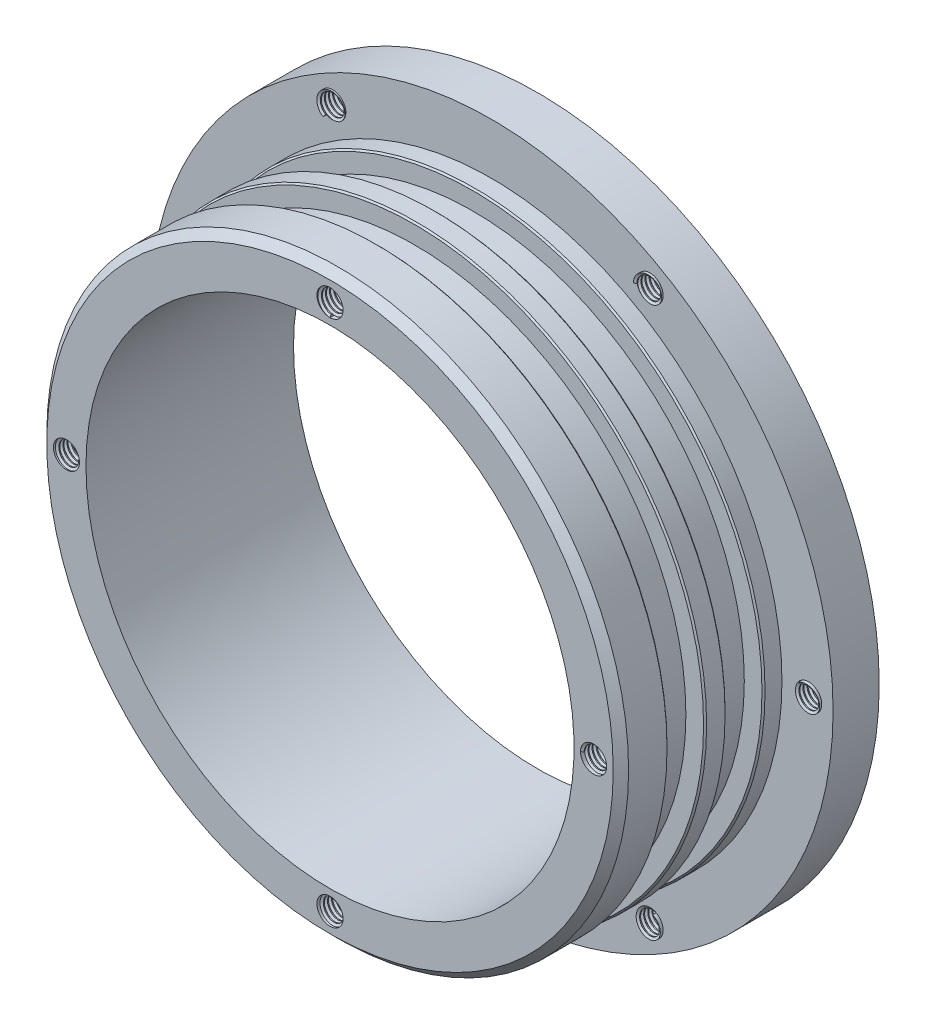
SolidWorks part; units mm, degrees
material "1060 Alloy"
ref_plane "Front Plane" through (0, 0, 0) normal (0, 0, 1) x (1, 0, 0)
ref_plane "Top Plane" through (0, 0, 0) normal (0, 1, 0) x (1, 0, 0)
ref_plane "Right Plane" through (0, 0, 0) normal (1, 0, 0) x (0, 0, -1)
sketch "Sketch1" plane through (0, 0, 0) normal (0, 1, 0) x (1, 0, 0)
  line L2 (37.8, 21) -> (44.45, 21)
  line L3 (44.45, 21) -> (44.45, 27)
  line L4 (44.45, 27) -> (0, 27)
  line L8 (37.846, 1) -> (37.846, 6)
  line L9 (37.646, 6.2) -> (35.3, 6.2)
  line L10 (35.3, 6.2) -> (35.3, 11)
  line L11 (35.3, 11) -> (37.6, 11)
  line L12 (37.8, 11.2) -> (37.8, 13.6)
  line L13 (37.6, 13.8) -> (35.3, 13.8)
  line L14 (35.3, 13.8) -> (35.3, 18.6)
  line L15 (35.3, 18.6) -> (37.6, 18.6)
  line L16 (37.8, 18.8) -> (37.8, 21)
  line L17 (0, 0) -> (0, 27)
  line L18 (0, 0) -> (36.846, 0)
  line L19 (36.846, 0) -> (37.846, 1)
  line L20 (37.846, 6) -> (37.646, 6.2)
  line L21 (37.6, 11) -> (37.8, 11.2)
  line L22 (37.8, 13.6) -> (37.6, 13.8)
  line L23 (37.6, 18.6) -> (37.8, 18.8)
  line L24 (35.3, 13.8) -> (35.3, 11) construction
  line L25 (37.8, 21) -> (37.8, 13.6) construction
  point P1 (37.846, 0)
  point P4 (0, 0)
  point P12 (37.846, 6.2)
  point P15 (37.8, 11)
  point P16 (37.8, 13.8)
  point P19 (37.8, 18.6)
  point P26 (35.3, 12.4)
  dimension "D1" = 2.4
  dimension "D2" = 44.45
  dimension "D3" = 6
  dimension "D4" = 2.8
  dimension "D5" = 4.8
  dimension "D6" = 2.5
  dimension "D7" = 37.846
  dimension "D8" = 27
  dimension "D9" = 35.3
revolve "Revolve1" add sketch "Sketch1" angle 360 about L17
sketch "Sketch2" plane through (0, 0, -27) normal (0, 0, -1) x (-1, 0, 0)
  circle A0 centre (0, 0) radius 31.75
  dimension "D1" = 63.5
extrude "Cut-Extrude1" cut sketch "Sketch2" against normal through all
sketch "Sketch3" plane through (0, 0, -27) normal (0, 0, -1) x (-1, 0, 0)
  circle A0 centre (0, 0) radius 38.1
  circle A1 centre (0, 0) radius 35.56
  dimension "D1" = 76.2
  dimension "D2" = 71.12
extrude "Cut-Extrude2" cut sketch "Sketch3" against normal blind 2.286
sketch "Sketch4" plane through (0, 0, -27) normal (0, 0, -1) x (-1, 0, 0)
  circle A0 centre (0, 0) radius 34.29 construction
  dimension "D1" = 68.58
sketch "Sketch8" plane through (0, 0, -27) normal (0, 0, -1) x (-1, 0, 0)
  line L0 (-44.45, 0) -> (44.45, 0) construction
  line L1 (0, 44.45) -> (0, -44.45) construction
  circle A0 centre (0, 0) radius 44.45 construction
  circle A1 centre (0, 0) radius 41.275 construction
  point P9 (0, 0)
  dimension "D1" = 82.55
hole_wizard "M3 Clearance Hole3" positions "3DSketch2" profile "Sketch9" hole size "M3" standard "ANSI Metric"
sketch3d "3DSketch2"
  line L0 (44.45, 0, -27) -> (-44.45, 0, -27) construction
  circle A0 centre (0, 0, -27) radius 41.275 construction
  point P0 (41.275, 0, -27)
  point P6 (0, 0, -68.275)
sketch "Sketch9" plane through (41.275, 0, -27) normal (1, 0, 0) x (0, 1, 0)
  line L0 (0, 0) -> (0, 13.7215)
  line L1 (0, 13.7215) -> (1.7, 12.7)
  line L2 (1.7, 12.7) -> (1.7, 0)
  line L5 (1.7, 0) -> (0, 0)
  line L10 (0, 13.7215) -> (-1.7, 12.7) construction
  line L11 (0, -6.35) -> (0, 107.95) construction
  dimension "Hole Dia." = 3.4
  dimension "Hole Depth" = 12.7
  dimension "Drill Angle" = 118
thread "Thread1" pitch 0.5292 start angle 0, offset 0, length 0, pitch 0.5292, diameter 3.4
ref_plane "Plane1" through (42.975, 0, -27) normal (0, -1, 0) x (1, 0, 0)
sketch "Thread Profile1" plane through (42.975, 0, -27) normal (0, -1, 0) x (1, 0, 0)
  line L0 (0, 0) -> (0, 0.5292) construction
  line L11 (0, 0) -> (0, 0.463)
  line L12 (0, 0.463) -> (-0.2864, 0.2977)
  line L13 (-0.2864, 0.2977) -> (-0.2864, 0.1654)
  line L15 (-0.2864, 0.1654) -> (0, 0)
  line L17 (-0.2864, 0.2315) -> (0, 0.2315) construction
  point P2 (0, 0)
  dimension "Pitch" = 0.5292
  dimension "Profile_Angle" = 60
  dimension "Profile_Land" = 0.1323
  dimension "Profile_Height" = 0.2864
pattern_circular "CirPattern1" count 6 over 360 about axis through (0, 0, -27) along (0, 0, 1) of "M3 Clearance Hole3", "Thread1"
hole_wizard "M3 Clearance Hole4" positions "Sketch20" profile "Sketch21" hole size "M3" standard "ANSI Metric"
sketch "Sketch20" plane through (0, 0, 0) normal (0, 0, 1) x (1, 0, 0)
  line L0 (0, 44.45) -> (0, -44.45) construction
  line L1 (44.45, 0) -> (-44.45, 0) construction
  circle A0 centre (0, 0) radius 34.29 construction
  point P0 (0, 34.29)
  point P6 (34.29, 0)
  point P10 (0, -34.29)
  point P12 (-34.29, 0)
sketch "Sketch21" plane through (0, 34.29, 0) normal (1, 0, 0) x (0, -1, 0)
  line L0 (0, 0) -> (0, 6.1015)
  line L1 (0, 6.1015) -> (1.7, 5.08)
  line L2 (1.7, 5.08) -> (1.7, 0)
  line L5 (1.7, 0) -> (0, 0)
  line L10 (0, 6.1015) -> (-1.7, 5.08) construction
  line L11 (0, -6.35) -> (0, 107.95) construction
  dimension "Hole Dia." = 3.4
  dimension "Hole Depth" = 5.08
  dimension "Drill Angle" = 118
thread "Thread2" pitch 0.5292 profile "Thread Profile2" start angle 0, offset 0, length 0, pitch 0.5292, diameter 3.4
ref_plane "Plane2" through (32.59, 0, 0) normal (0, -1, 0) x (-1, 0, 0)
sketch "Thread Profile2" plane through (32.59, 0, 0) normal (0, -1, 0) x (-1, 0, 0)
  line L0 (0, 0) -> (0, 0.5292) construction
  line L11 (0, 0) -> (0, 0.463)
  line L12 (0, 0.463) -> (-0.2864, 0.2977)
  line L13 (-0.2864, 0.2977) -> (-0.2864, 0.1654)
  line L15 (-0.2864, 0.1654) -> (0, 0)
  line L17 (-0.2864, 0.2315) -> (0, 0.2315) construction
  point P2 (0, 0)
  dimension "Pitch" = 0.5292
  dimension "Profile_Angle" = 60
  dimension "Profile_Land" = 0.1323
  dimension "Profile_Height" = 0.2864
pattern_circular "CirPattern2" count 4 over 360 about axis through (0, 0, 0) along (0, 0, 1) of "Thread2"
